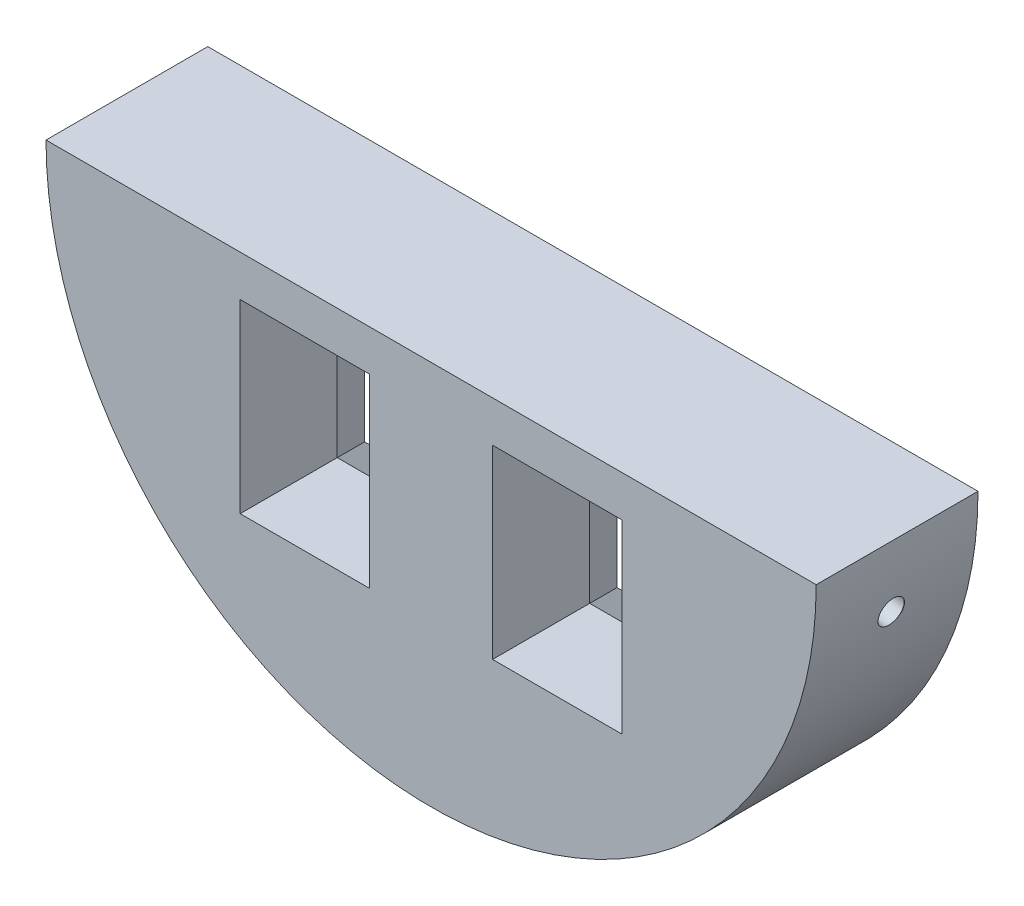
SolidWorks part; units mm, degrees
ref_plane "Front Plane" through (0, 0, 0) normal (0, 0, 1) x (1, 0, 0)
ref_plane "Top Plane" through (0, 0, 0) normal (0, 1, 0) x (1, 0, 0)
ref_plane "Right Plane" through (0, 0, 0) normal (1, 0, 0) x (0, 0, -1)
sketch "Sketch1" plane through (0, 0, 0) normal (0, 0, 1) x (1, 0, 0)
  line L0 (-119, 0) -> (0, 0)
  line L3 (-50, -35) -> (-30, -35)
  line L4 (-50, -35) -> (-50, -15)
  line L5 (-50, -15) -> (-30, -15)
  line L6 (-30, -35) -> (-30, -15)
  line L7 (-89, -35) -> (-69, -35)
  line L8 (-89, -35) -> (-89, -15)
  line L9 (-89, -15) -> (-69, -15)
  line L10 (-69, -35) -> (-69, -15)
  arc A1 (-119, 0) -> (0, 0) centre (-59.5, 0) ccw
  dimension "D1" = 30
  dimension "D7" = 59.5
  dimension "D2" = 15
  dimension "D3" = 30
  dimension "D4" = 20
extrude "Boss-Extrude1" add sketch "Sketch1" along normal blind 25
hole_wizard "Ø4.0mm Dowel Hole2" positions "3DSketch2" profile "Sketch4" hole size "Ø4.0" standard "ANSI Metric"
sketch3d "3DSketch2"
  line L2 (0, 0, 25) -> (0, 0, 0) construction
  line L4 (0, 0, 25) -> (0, 0, 0) construction
  line L5 (0, 0, 12.5) -> (-0.9039, -10.3321, 12.5) construction
  line L8 (-59.5, 0, 0) -> (-59.5, 0, 25) construction
  line L9 (0, 0, 0) -> (-119, 0, 0) construction
  line L10 (0, 0, 25) -> (-119, 0, 25) construction
  line L12 (-59.5, 0, 12.5) -> (-0.9039, -10.3321, 12.5) construction
  line L16 (-59.5, 0, 12.5) -> (0, 0, 12.5) construction
  point P0 (-0.9039, -10.3321, 12.5)
  point P16 (-0.9039, -10.3321, 12.5)
  point P23 (-0.9039, -10.3321, 12.5)
  point P25 (-0.9039, -10.3321, 12.5)
  dimension "D1" = 10
sketch "Sketch4" plane through (-0.9039, -10.3321, 12.5) normal (0, 0, 1) x (0.1736, 0.9848, 0)
  line L0 (0, 0) -> (0, 11.2017)
  line L1 (0, 11.2017) -> (2, 10)
  line L2 (2, 10) -> (2, 0.025)
  line L3 (2, 0.025) -> (2.025, 0)
  line L5 (2.025, 0) -> (0, 0)
  line L6 (-2, 0.025) -> (-2.025, 0) construction
  line L10 (0, 11.2017) -> (-2, 10) construction
  line L11 (0, -6.35) -> (0, 107.95) construction
  dimension "Hole Dia." = 4
  dimension "Hole Depth" = 10
  dimension "Near C'Sink Dia." = 4.05
  dimension "Near C'Sink Angle" = 90
  dimension "Drill Angle" = 118
pattern_circular "CirPattern1" count 5 over 160 about axis through (-59.5, 0, 0) along (0, 0, 1) of "Ø4.0mm Dowel Hole2" reverse direction yes
chamfer "Chamfer1" distance 15 angle 30 2 edges at (-79, -15, 25) (-40, -15, 25) first distance on face at (-79, -15, 12.5) first distance on face at (-40, -15, 12.5)
chamfer "Chamfer2" distance 10 angle 30 8 edges at (-40, -35, 0) (-79, -35, 0) (-50, -25, 0) (-40, -15, 0) (-30, -25, 0) (-89, -25, 0) (-79, -15, 0) (-69, -25, 0) first distance on face at (-40, -35, 12.5) first distance on face at (-79, -35, 12.5) first distance on face at (-50, -21.2679, 12) first distance on face at (-40, -15, 5) first distance on face at (-30, -21.2679, 12) first distance on face at (-89, -21.2679, 12) first distance on face at (-79, -15, 5) first distance on face at (-69, -21.2679, 12)
